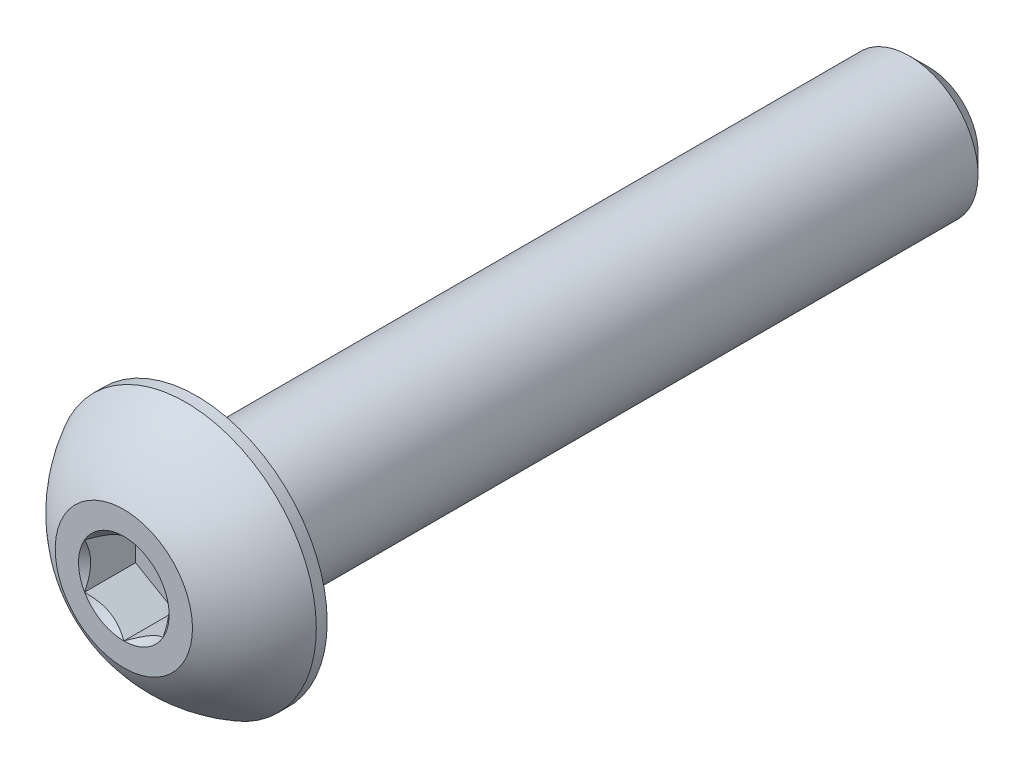
SolidWorks part; units mm, degrees
ref_plane "Front" through (0, 0, 0) normal (0, 0, 1) x (1, 0, 0)
ref_plane "Top" through (0, 0, 0) normal (0, 1, 0) x (1, 0, 0)
ref_plane "Right" through (0, 0, 0) normal (1, 0, 0) x (0, 0, -1)
sketch "Sketch1" plane through (0, 0, 0) normal (1, 0, 0) x (0, 0, -1)
  line L2 (2.2098, 2.0828) -> (24.4348, 2.0828)
  line L3 (24.4348, 2.0828) -> (24.4348, 0)
  line L4 (24.4348, 0) -> (2.2098, 0)
  line L6 (1.8783, 3.9624) -> (2.2098, 3.9624) construction
  line L7 (24.4348, 2.0828) -> (24.4348, -2.0828) construction
  line L8 (0, 0) -> (2.2098, 0) construction
  line L9 (2.2098, 3.9624) -> (2.2098, -3.9624) construction
  line L11 (2.2098, 2.0828) -> (2.2098, 0)
  line L13 (0, 1.1906) -> (0, -1.1906) construction
  line L14 (0, 1.1906) -> (0, 2.0828) construction
  arc A3 (0, 2.0828) -> (1.8783, 3.9624) centre (3.9638, 0) cw construction
  dimension "D1" = 0.3315
revolve "Revolve1" add sketch "Sketch1" angle 360 mid plane about L4
sketch "Sketch3" plane through (0, 0, -24.4348) normal (0, 0, -1) x (-1, 0, 0)
  circle A0 centre (0, 0) radius 2.0828
curve "Helix/Spiral1" pitch 0.7937 height 23.0188 turns 29
sketch "Sketch2" plane through (0, 0, 0) normal (1, 0, 0) x (0, 0, -1)
  line L0 (24.4348, 2.0828) -> (25.1293, 2.0828)
  line L1 (25.1293, 2.0828) -> (24.8317, 1.5672)
  line L2 (24.8317, 1.5672) -> (24.7325, 1.5672)
  line L3 (24.7325, 1.5672) -> (24.4348, 2.0828)
  line L4 (24.5836, 1.825) -> (24.9805, 1.825) construction
  dimension "D1" = 60
  dimension "D2" = 0.0992
  dimension "D3" = 0.3969
chamfer "Chamfer1" distance 0.5953 angle 45 1 edges at (0, 2.0828, -24.4348)
sweep "Cut-Sweep1" [suppressed] cut profiles "Sketch2" path "Helix/Spiral1"
sketch "Sketch7" plane through (0, 0, 0) normal (1, 0, 0) x (0, 0, -1)
  line L6 (1.8783, 3.9624) -> (2.2098, 3.9624) construction
  line L8 (0, 0) -> (2.2098, 0) construction
  line L11 (2.2098, 3.9624) -> (2.2098, -3.9624) construction
  line L12 (1.8783, 3.9624) -> (2.2098, 3.9624)
  line L13 (0, 0) -> (2.2098, 0)
  line L14 (0, 1.1906) -> (0, -1.1906) construction
  line L15 (2.2098, 3.9624) -> (2.2098, 0)
  line L16 (0, 2.0828) -> (0, 0)
  arc A2 (1.8783, 3.9624) -> (0, 2.0828) centre (3.9638, 0) ccw construction
  arc A3 (1.8783, 3.9624) -> (0, 2.0828) centre (3.9638, 0) ccw
revolve "Revolve2" add sketch "Sketch7" angle 360 mid plane about L13
sketch "Sketch5" plane through (0, 0, 0) normal (0, 0, 1) x (1, 0, 0)
  line L1 (1.1906, -0.6874) -> (1.1906, 0.6874)
  line L2 (1.1906, 0.6874) -> (0, 1.3748)
  line L3 (0, 1.3748) -> (-1.1906, 0.6874)
  line L4 (-1.1906, 0.6874) -> (-1.1906, -0.6874)
  line L5 (-1.1906, -0.6874) -> (0, -1.3748)
  line L6 (0, -1.3748) -> (1.1906, -0.6874)
  circle A0 centre (0, 0) radius 1.1906 construction
extrude "Cut-Extrude2" cut sketch "Sketch5" against normal blind 1.5469
sketch "Sketch6" plane through (0, 0, 0) normal (0, 0, 1) x (1, 0, 0)
  circle A0 centre (0, 0) radius 1.3748
extrude "Cut-Extrude3" cut sketch "Sketch6" against normal blind 1.5469 draft 45
sketch "Sketch9" [suppressed] plane through (0, 0, -1.4986) normal (0, 0, 1) x (1, 0, 0)
  circle A2 centre (0, 0) radius 1.4224
extrude "Boss-Extrude2" [suppressed] add sketch "Sketch9" against normal offset from surface (12.7 mm away) 31.75
sketch "Sketch10" plane through (0, 0, 0) normal (1, 0, 0) x (0, 0, -1)
  line L0 (24.4348, 2.0828) -> (24.4348, -2.0828) construction
  point P0 (23.2442, -2.0828)
  dimension "D1" = 1.1906
equation "\"D3@Helix/Spiral1\" = \"Lg@Sketch1\" + \"D4@Helix/Spiral1\""
equation "\"D2@Sketch2\" = \"D4@Helix/Spiral1\" * .125"
equation "\"D3@Sketch2\" = \"D4@Helix/Spiral1\" * .5"
equation "\"D1@Chamfer1\" = \"D4@Helix/Spiral1\" * .75"
equation "\"D1@Cut-Extrude2\" = \"Head Ht@Sketch1\" * .7"
equation "\"D1@Sketch1\" = \"Head Ht@Sketch1\" * .15"
equation "\"D1@Sketch10\" = \"D4@Helix/Spiral1\" * 1.5"
equation "\"D1@Cut-Extrude3\" = \"D1@Cut-Extrude2\""
